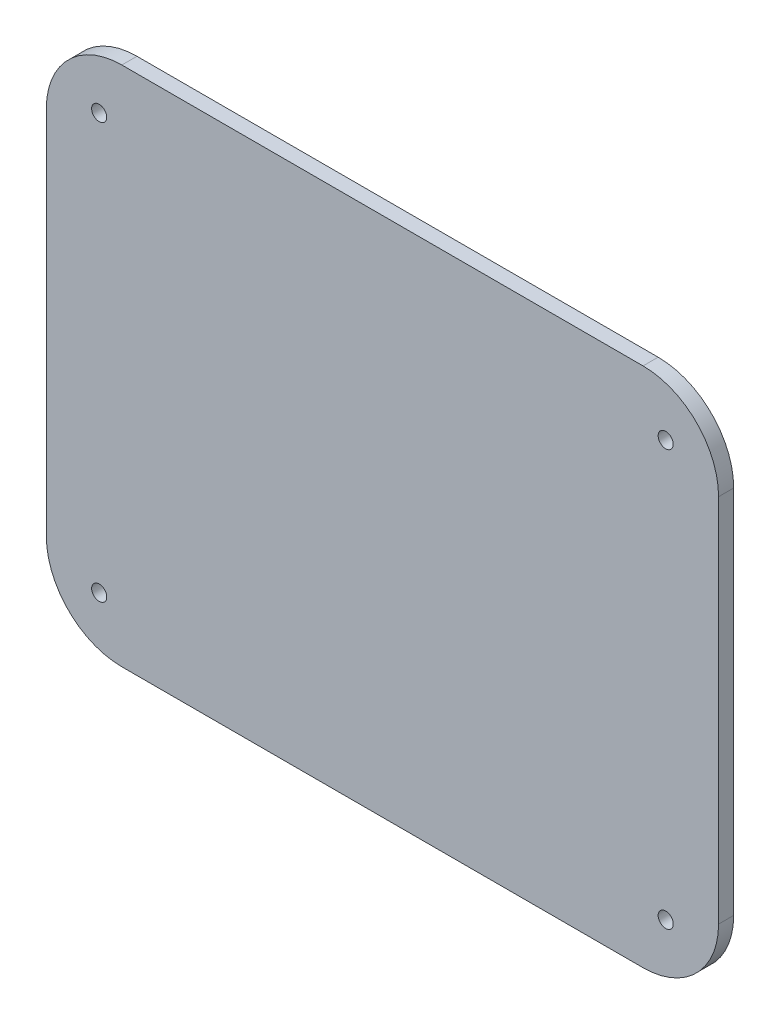
SolidWorks part; units mm, degrees
ref_plane "前视基准面" through (0, 0, 0) normal (0, 0, 1) x (1, 0, 0)
ref_plane "上视基准面" through (0, 0, 0) normal (0, 1, 0) x (1, 0, 0)
ref_plane "右视基准面" through (0, 0, 0) normal (1, 0, 0) x (0, 0, -1)
sketch "草图1" plane through (0, 0, 0) normal (0, 0, 1) x (1, 0, 0)
  line L0 (10, 0) -> (10, -10)
  line L1 (10, 0) -> (79, 0)
  line L2 (0, -10) -> (0, -59)
  line L3 (10, -69) -> (79, -69)
  line L4 (89, -10) -> (89, -59)
  line L5 (10, -10) -> (0, -10)
  line L6 (44.5, 0) -> (44.5, -69) construction
  line L7 (0, -34.5) -> (89, -34.5)
  line L8 (79, -10) -> (89, -10)
  line L9 (79, 0) -> (79, -10)
  line L10 (79, -59) -> (89, -59)
  line L11 (79, -69) -> (79, -59)
  line L12 (10, -59) -> (0, -59)
  line L13 (10, -69) -> (10, -59)
  arc A0 (79, 0) -> (89, -10) centre (79, -10) cw
  arc A1 (0, -59) -> (10, -69) centre (10, -59) ccw
  arc A2 (79, -69) -> (89, -59) centre (79, -59) ccw
  arc A3 (10, 0) -> (0, -10) centre (10, -10) ccw
  circle A4 centre (7, -7) radius 1
  circle A5 centre (82, -7) radius 1
  circle A6 centre (82, -62) radius 1
  circle A7 centre (7, -62) radius 1
  point P7 (89, 0)
  point P10 (0, -69)
  point P15 (0, 0)
  dimension "D3" = 10
  dimension "D5" = 3
  dimension "D6" = 2
  dimension "D1" = 89
  dimension "D2" = 69
  dimension "D4" = 3
extrude "凸台-拉伸1" add sketch "草图1" against normal blind 2 contours L6 L1 L0 L5 L2 L7 | L1 L6 L7 L4 L8 L9 | L6 L7 L2 L12 L13 L3 | L7 L6 L3 L11 L10 L4 | L0 A3 L5 A4 | A0 L9 L8 A5 | L12 A1 L13 A7 | L11 A2 L10 A6 region at (23.4519, -18.1035, 0) region at (5.704, -5.704, 0) region at (65.5481, -18.1035, 0) region at (83.296, -5.704, 0) region at (65.5481, -50.8965, 0) region at (23.4519, -50.8965, 0) region at (5.704, -63.296, 0) region at (83.296, -63.296, 0)
